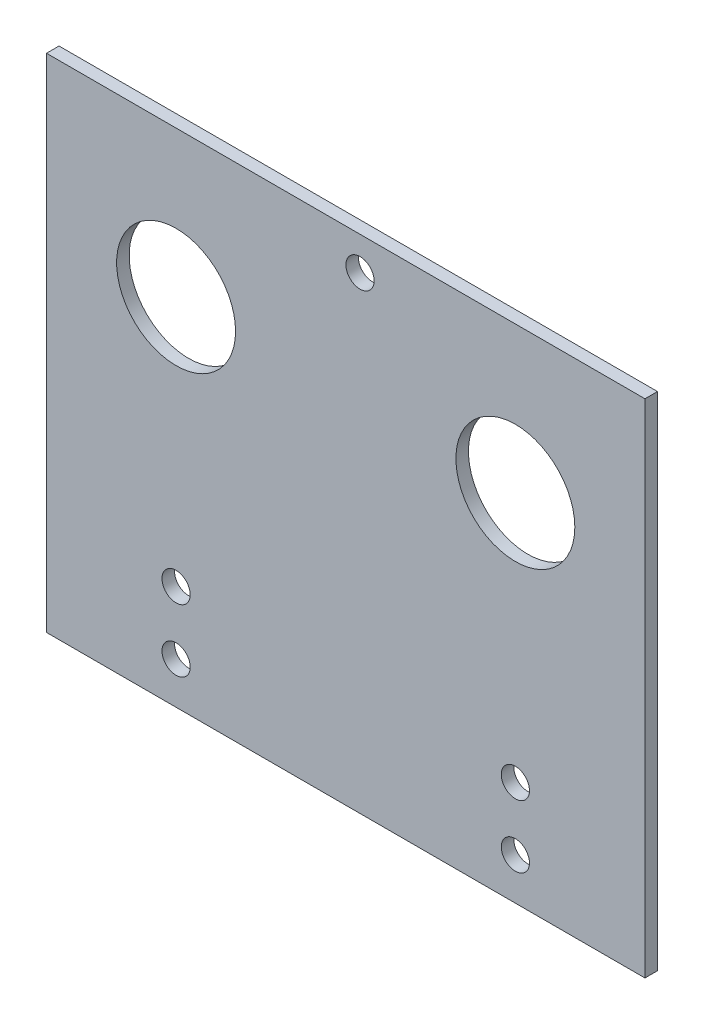
SolidWorks part; units mm, degrees
ref_plane "Front Plane" through (0, 0, 0) normal (0, 0, 1) x (1, 0, 0)
ref_plane "Top Plane" through (0, 0, 0) normal (0, 1, 0) x (1, 0, 0)
ref_plane "Right Plane" through (0, 0, 0) normal (1, 0, 0) x (0, 0, -1)
sketch "Sketch1" plane through (0, 0, 0) normal (0, 0, 1) x (1, 0, 0)
  line L1 (0, 0) -> (143.16, 0)
  line L2 (0, 0) -> (0, -120)
  line L3 (0, -120) -> (143.16, -120)
  line L4 (143.16, 0) -> (143.16, -120)
  dimension "D1" = 120
  dimension "D2" = 143.16
extrude "Boss-Extrude1" add sketch "Sketch1" along normal blind 3
sketch "Sketch2" plane through (0, 0, 3) normal (0, 0, 1) x (1, 0, 0)
  line L0 (0, 0) -> (0, -120) construction
  line L1 (143.16, -120) -> (143.16, 0) construction
  line L2 (0, -120) -> (143.16, -120) construction
  line L3 (143.16, 0) -> (0, 0) construction
  circle A0 centre (31, -35) radius 14.225
  circle A1 centre (112.16, -35) radius 14.225
  circle A3 centre (31, -110) radius 3.375
  circle A4 centre (112.16, -110) radius 3.375
  circle A7 centre (75, -8) radius 3.375
  circle A8 centre (31, -95) radius 3.375
  circle A9 centre (112.16, -95) radius 3.375
  dimension "D1" = 28.45
  dimension "D2" = 28.45
  dimension "D3" = 10
  dimension "D4" = 6.75
  dimension "D5" = 6.75
  dimension "D7" = 6.75
  dimension "D8" = 75
  dimension "D14" = 6.75
  dimension "D17" = 6.75
  dimension "D9" = 31
  dimension "D10" = 31
  dimension "D12" = 35
  dimension "D13" = 8
  dimension "D15" = 15
  dimension "D16" = 15
extrude "Cut-Extrude1" cut sketch "Sketch2" against normal through all
